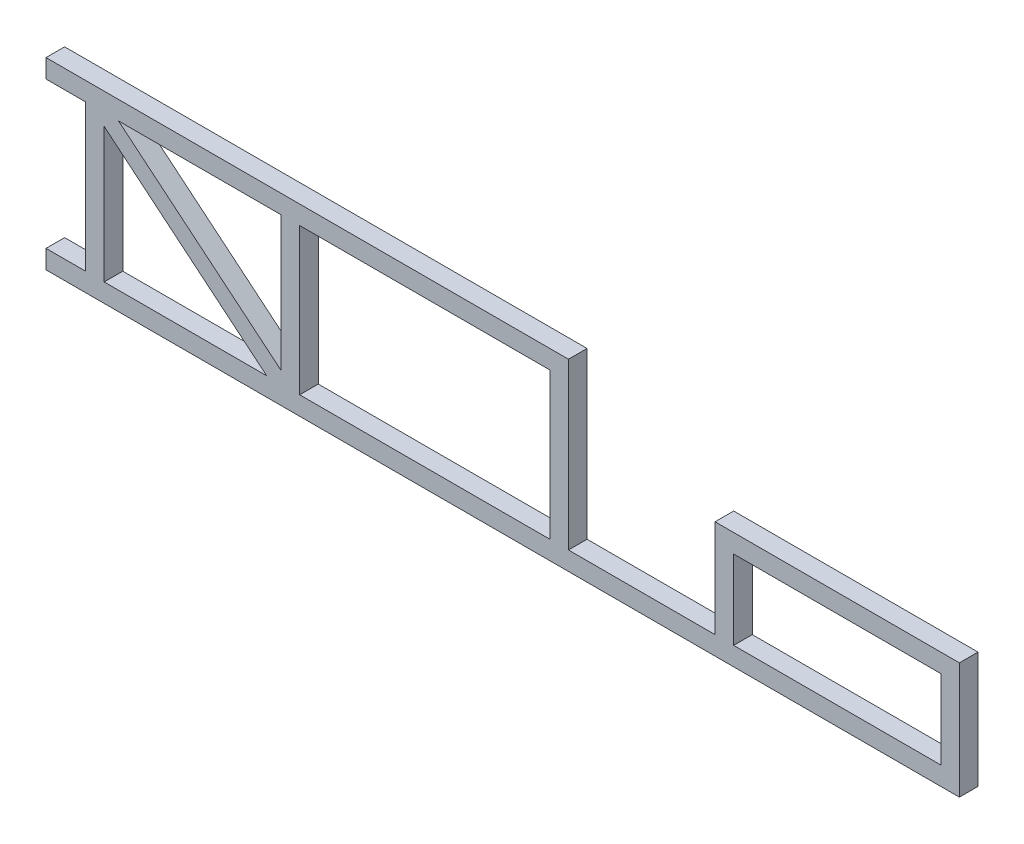
SolidWorks part; units mm, degrees
material "AISI 1020"
ref_plane "Front Plane" through (0, 0, 0) normal (0, 0, 1) x (1, 0, 0)
ref_plane "Top Plane" through (0, 0, 0) normal (0, 1, 0) x (1, 0, 0)
ref_plane "Right Plane" through (0, 0, 0) normal (1, 0, 0) x (0, 0, -1)
sketch "Sketch1" plane through (0, 0, 0) normal (0, 0, 1) x (1, 0, 0)
  line L9 (1850, 38.1) -> (1069.1, 38.1) construction
  line L10 (0, 0) -> (1850, 0)
  line L11 (0, 0) -> (0, 38.1)
  line L12 (0, 38.1) -> (80.95, 38.1)
  line L18 (119.05, 38.1) -> (119.05, 338.1) construction
  line L23 (519.05, 38.1) -> (519.05, 338.1)
  line L24 (119.05, 338.1) -> (480.95, 38.1) construction
  line L25 (80.95, 188.1) -> (119.05, 188.1) construction
  line L27 (80.95, 38.1) -> (80.95, 338.1)
  line L31 (451.6178, 38.1) -> (119.05, 38.1)
  line L32 (119.05, 38.1) -> (480.95, 338.1) construction
  line L33 (314.6661, 200.2576) -> (285.3339, 175.9424) construction
  line L34 (148.3822, 338.1) -> (480.95, 338.1)
  line L35 (480.95, 62.4152) -> (480.95, 338.1)
  line L36 (0, 376.2) -> (1069.1, 376.2)
  line L37 (0, 376.2) -> (0, 338.1)
  line L38 (0, 338.1) -> (80.95, 338.1)
  line L39 (1069.1, 376.2) -> (1069.1, 338.1)
  line L40 (519.05, 338.1) -> (1031, 338.1)
  line L41 (380.6464, 145.5627) -> (430.6765, 104.0898) construction
  line L42 (360.2948, 113.8029) -> (394.9416, 85.0821) construction
  line L43 (148.3822, 338.1) -> (480.95, 62.4152)
  line L44 (119.05, 313.7848) -> (451.6178, 38.1)
  line L47 (119.05, 313.7848) -> (119.05, 38.1)
  line L48 (519.05, 188.1) -> (480.95, 188.1) construction
  line L52 (1069.1, 338.1) -> (1069.1, 38.1)
  line L53 (1031, 338.1) -> (1031, 38.1)
  line L55 (1031, 38.1) -> (519.05, 38.1)
  line L56 (1850, 38.1) -> (1850, 0) construction
  line L57 (1850, 38.1) -> (1869.05, 38.1) construction
  line L59 (1850, 0) -> (1869.05, 0)
  line L60 (1869.05, 38.1) -> (1869.05, 0)
  line L62 (1869.05, 38.1) -> (1830.95, 38.1) construction
  line L63 (1869.05, 38.1) -> (1869.05, 0) construction
  line L64 (1869.05, 0) -> (1830.95, 0) construction
  line L65 (1830.95, 38.1) -> (1830.95, 0) construction
  line L70 (1369.05, 238.1) -> (1869.05, 238.1)
  line L71 (1869.05, 238.1) -> (1869.05, 38.1)
  line L72 (1830.95, 200) -> (1830.95, 38.1)
  line L73 (1069.1, 38.1) -> (1830.95, 38.1) construction
  line L81 (1407.15, 38.1) -> (1369.05, 38.1) construction
  line L84 (1830.95, 38.1) -> (1407.15, 38.1)
  line L85 (1369.05, 38.1) -> (1069.1, 38.1)
  line L86 (1369.05, 238.1) -> (1369.05, 38.1)
  line L87 (1830.95, 238.1) -> (1830.95, 200) construction
  line L88 (1407.15, 200) -> (1407.15, 38.1)
  line L89 (1407.15, 200) -> (1830.95, 200)
  point P4 (100, 38.1)
  point P7 (500, 38.1)
  point P9 (300, 188.1)
  point P11 (500, 38.1)
  point P23 (500, 338.1)
  point P25 (100, 338.1)
  point P26 (100, 188.1)
  point P28 (300, 188.1)
  point P29 (300, 188.1)
  point P33 (148.3822, 338.1)
  point P34 (285.3339, 175.9424)
  point P35 (119.05, 313.7848)
  point P37 (480.95, 62.4152)
  point P38 (451.6178, 38.1)
  point P44 (119.05, 313.7848)
  point P46 (500, 188.1)
  point P51 (1069.1, 38.1)
  point P52 (1069.1, 338.1)
  point P54 (1830.95, 38.1)
  point P56 (1850, 19.05)
  point P59 (1850, 219.05)
  point P60 (1850, 219.05)
  point P64 (1830.95, 238.1)
  point P65 (1407.15, 200)
  point P66 (1830.95, 38.1)
  point P67 (1830.95, 219.05)
  point P71 (1369.05, 238.1)
  point P72 (1869.05, 19.05)
  dimension "D1" = 1850
  dimension "D3" = 100
  dimension "D6" = 500
  dimension "D9" = 100
  dimension "D10" = 569.1
  dimension "D5" = 300
  dimension "D14" = 19.05
  dimension "D2" = 200
  dimension "D4" = 500
extrude "Boss-Extrude1" add sketch "Sketch1" against normal blind 38.1
shell "Shell1" thickness 3.175
equation "\"D14@Sketch1\"=\"Cross_Section_1\"/2"
